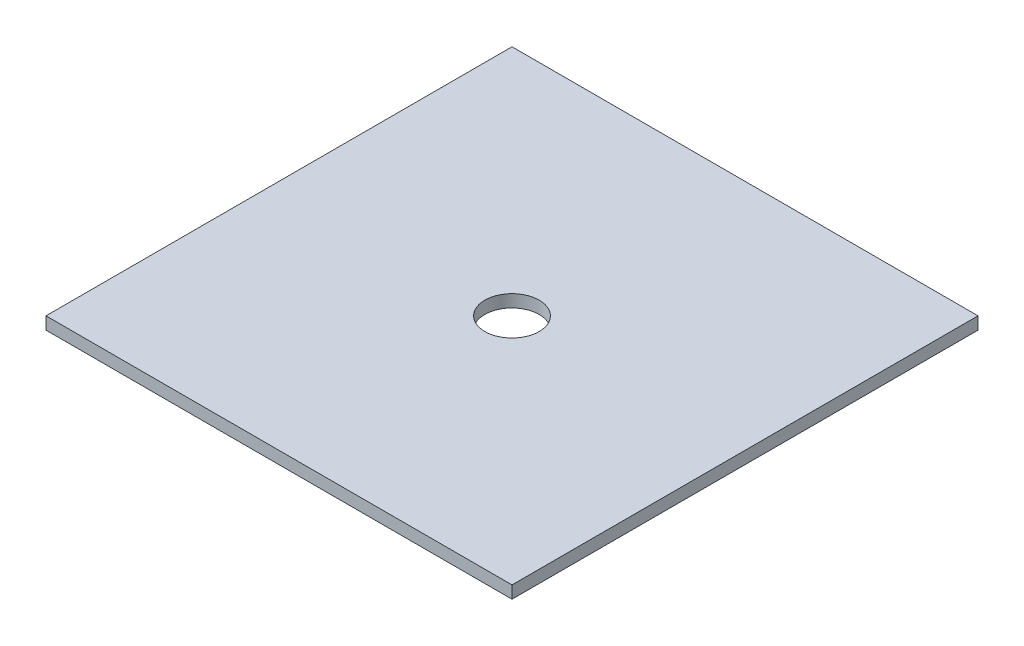
SolidWorks part; units mm, degrees
ref_plane "Plan de face" through (0, 0, 0) normal (0, 0, 1) x (1, 0, 0)
ref_plane "Plan de dessus" through (0, 0, 0) normal (0, 1, 0) x (1, 0, 0)
ref_plane "Plan de droite" through (0, 0, 0) normal (1, 0, 0) x (0, 0, -1)
sketch "Esquisse1" plane through (0, 0, 0) normal (0, 1, 0) x (1, 0, 0)
  line L1 (-150, -150) -> (150, -150)
  line L2 (-150, -150) -> (-150, 150)
  line L3 (-150, 150) -> (150, 150)
  line L4 (150, -150) -> (150, 150)
  line L5 (-150, -150) -> (150, 150) construction
  line L6 (-150, 150) -> (150, -150) construction
  point P0 (0, 0)
  dimension "D1" = 300
extrude "Boss.-Extru.1" add sketch "Esquisse1" along normal blind 8
sketch "Esquisse2" plane through (0, 8, 0) normal (0, 1, 0) x (1, 0, 0)
  circle A0 centre (0, 0) radius 17.5
  dimension "D1" = 35
extrude "Enlèv. mat.-Extru.1" cut sketch "Esquisse2" against normal through all both and the other way through all
